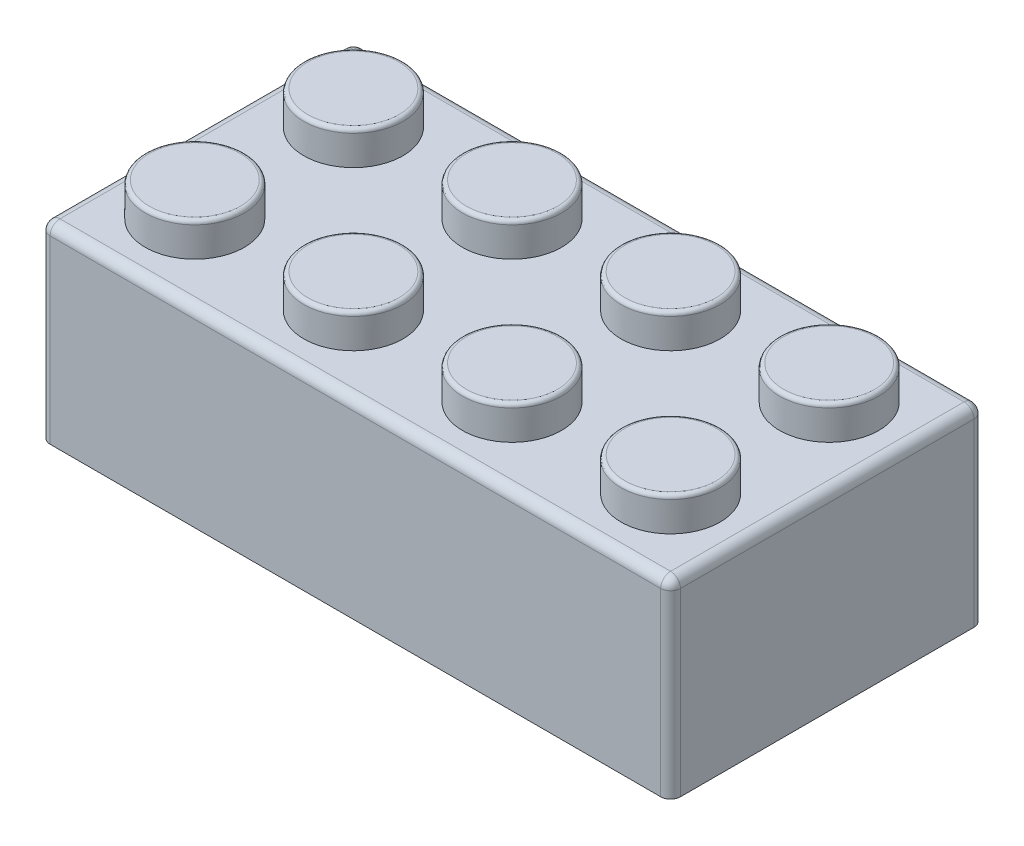
SolidWorks part; units mm, degrees
ref_plane "Front Plane" through (0, 0, 0) normal (0, 0, 1) x (1, 0, 0)
ref_plane "Top Plane" through (0, 0, 0) normal (0, 1, 0) x (1, 0, 0)
ref_plane "Right Plane" through (0, 0, 0) normal (1, 0, 0) x (0, 0, -1)
sketch "Sketch2" plane through (0, 0, 0) normal (0, 1, 0) x (1, 0, 0)
  line L1 (-15.3292, 8.7165) -> (16.4708, 8.7165)
  line L2 (-15.3292, 8.7165) -> (-15.3292, -7.0835)
  line L3 (-15.3292, -7.0835) -> (16.4708, -7.0835)
  line L4 (16.4708, 8.7165) -> (16.4708, -7.0835)
  dimension "D1" = 31.8
  dimension "D2" = 15.8
extrude "Boss-Extrude1" add sketch "Sketch2" along normal blind 9.6 contours L2 L1 L4 L3
fillet "Fillet1" radius 0.5 4 edges at (16.4708, 9.6, -0.8165) (0.5708, 9.6, 7.0835) (-15.3292, 9.6, -0.8165) (0.5708, 9.6, -8.7165)
fillet "Fillet3" radius 0.5 8 edges at (-15.1827, 9.4536, 6.9371) (16.3244, 9.4536, 6.9371) (-15.1827, 9.4536, -8.57) (16.3244, 9.4536, -8.57) (-15.3292, 4.55, 7.0835) (16.4708, 4.55, 7.0835) (-15.3292, 4.55, -8.7165) (16.4708, 4.55, -8.7165)
sketch "Sketch4" plane through (0, 0, 0) normal (0, -1, 0) x (1, 0, 0)
  line L0 (-15.3292, -8.2165) -> (-15.3292, 6.5835) construction
  line L1 (-13.8392, 5.5935) -> (14.9808, 5.5935)
  line L2 (-13.8392, 5.5935) -> (-13.8392, -7.2265)
  line L3 (-13.8392, -7.2265) -> (14.9808, -7.2265)
  line L4 (14.9808, 5.5935) -> (14.9808, -7.2265)
  line L5 (-14.8292, 7.0835) -> (15.9708, 7.0835) construction
  line L6 (-14.8292, -8.7165) -> (15.9708, -8.7165) construction
  line L7 (16.4708, -8.2165) -> (16.4708, 6.5835) construction
  dimension "D1" = 1.49
  dimension "D2" = 1.49
  dimension "D3" = 1.49
  dimension "D4" = 1.49
extrude "Cut-Extrude1" cut sketch "Sketch4" against normal blind 8.1
sketch "Sketch6" plane through (0, 9.6, 0) normal (0, 1, 0) x (1, 0, 0)
  line L0 (-14.8292, 8.7165) -> (15.9708, 8.7165) construction
  line L1 (-15.3292, -6.5835) -> (-15.3292, 8.2165) construction
  circle A0 centre (-11.4292, 4.8165) radius 2.5
  dimension "D1" = 3.9
  dimension "D2" = 3.9
extrude "Boss-Extrude3" add sketch "Sketch6" along normal blind 1.7
fillet "Fillet2" radius 0.2 1 edges at (-11.4292, 11.3, -2.3165)
pattern_linear "LPattern3" count 4 spacing 8 along (1, 0, 0) count 2 spacing 8 along (0, 0, 1) of "Boss-Extrude3", "Fillet2"
sketch "Sketch8" plane through (0, 8.1, 0) normal (0, -1, 0) x (1, 0, 0)
  line L0 (16.4708, -8.2165) -> (16.4708, 6.5835) construction
  line L1 (-14.8292, -8.7165) -> (15.9708, -8.7165) construction
  circle A0 centre (8.5708, -0.8165) radius 3.155
  dimension "D1" = 7.9
  dimension "D2" = 7.9
extrude "Boss-Extrude4" add sketch "Sketch8" along normal blind 8.1 contours A0
sketch "Sketch9" plane through (0, 0, 0) normal (0, -1, 0) x (1, 0, 0)
  line L0 (16.4708, -8.2165) -> (16.4708, 6.5835) construction
  circle A0 centre (8.5708, -0.8165) radius 2.655
  circle A1 centre (8.5708, -0.8165) radius 3.155 construction
  dimension "D1" = 0.5
extrude "Cut-Extrude2" cut sketch "Sketch9" against normal blind 8.1
pattern_linear "LPattern4" count 3 spacing 8 along (-1, 0, 0) of "Boss-Extrude4", "Cut-Extrude2"
